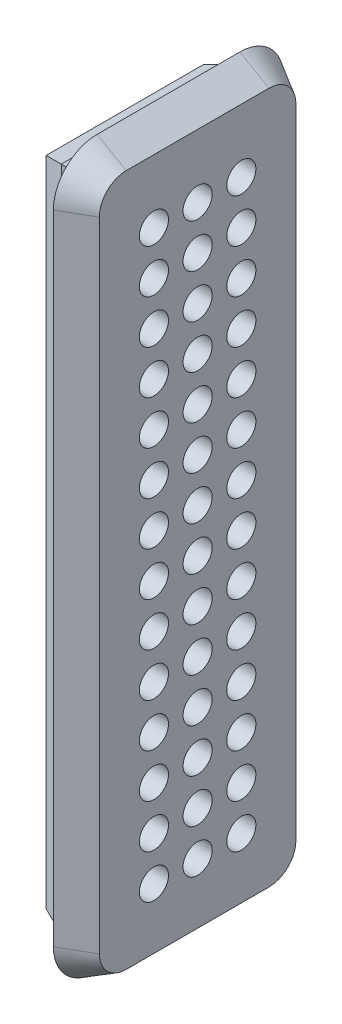
SolidWorks part; units mm, degrees
ref_plane "前视基准面" through (0, 0, 0) normal (0, 0, 1) x (1, 0, 0)
ref_plane "上视基准面" through (0, 0, 0) normal (0, 1, 0) x (1, 0, 0)
ref_plane "右视基准面" through (0, 0, 0) normal (1, 0, 0) x (0, 0, -1)
other "Configuration Table"
sketch "草图1" plane through (0, 0, 0) normal (1, 0, 0) x (0, 0, -1)
  line L0 (-147.2592, 68.0612) -> (-135.4592, 68.0612)
  line L1 (-147.3592, 68.1612) -> (-135.3592, 68.1612) construction
  line L2 (-147.3592, 68.1612) -> (-147.3592, 22.1612) construction
  line L3 (-147.3592, 22.1612) -> (-135.3592, 22.1612) construction
  line L4 (-135.3592, 68.1612) -> (-135.3592, 22.1612) construction
  line L5 (-135.4592, 68.0612) -> (-135.4592, 22.2612)
  line L6 (-147.2592, 22.2612) -> (-135.4592, 22.2612)
  line L7 (-147.2592, 68.0612) -> (-147.2592, 22.2612)
  line L8 (-145.7592, 66.5612) -> (-145.7592, 23.7612)
  line L9 (-145.7592, 23.7612) -> (-136.9592, 23.7612)
  line L10 (-136.9592, 66.5612) -> (-136.9592, 23.7612)
  line L11 (-145.7592, 66.5612) -> (-136.9592, 66.5612)
  dimension "D1" = 12
  dimension "D2" = 46
  dimension "D3" = 0.1
  dimension "D4" = 1.5
extrude "凸台-拉伸1" add sketch "草图1" along normal blind 3
sketch "草图2" plane through (3, 0, 0) normal (1, 0, 0) x (0, 0, -1)
  line L12 (-149.2592, 20.2612) -> (-133.4592, 20.2612)
  line L13 (-149.2592, 70.0612) -> (-149.2592, 20.2612)
  line L14 (-133.4592, 70.0612) -> (-149.2592, 70.0612)
  line L15 (-133.4592, 20.2612) -> (-133.4592, 70.0612)
  line L16 (-146.2592, 20.2612) -> (-136.4592, 20.2612)
  line L17 (-149.2592, 67.0612) -> (-149.2592, 23.2612)
  line L18 (-136.4592, 70.0612) -> (-146.2592, 70.0612)
  line L19 (-133.4592, 23.2612) -> (-133.4592, 67.0612)
  arc A0 (-136.4592, 70.0612) -> (-133.4592, 67.0612) centre (-136.4592, 67.0612) cw
  arc A1 (-136.4592, 20.2612) -> (-133.4592, 23.2612) centre (-136.4592, 23.2612) ccw
  arc A2 (-146.2592, 20.2612) -> (-149.2592, 23.2612) centre (-146.2592, 23.2612) cw
  arc A3 (-149.2592, 67.0612) -> (-146.2592, 70.0612) centre (-146.2592, 67.0612) cw
  dimension "D2" = 3
  dimension "D1" = 2
extrude "凸台-拉伸2" add sketch "草图2" along normal blind 2 draft 30
sketch "草图3" plane through (3, 0, 0) normal (-1, 0, 0) x (0, 0, 1)
  line L0 (136.4592, 70.0612) -> (146.2592, 70.0612) construction
  circle A1 centre (144.3592, 64.5612) radius 1
  circle A2 centre (141.3592, 64.5612) radius 1
  circle A3 centre (138.3592, 64.5612) radius 1
  circle A4 centre (141.3592, 61.5612) radius 1
  circle A5 centre (138.3592, 61.5612) radius 1
  circle A6 centre (141.3592, 58.5612) radius 1
  circle A7 centre (138.3592, 58.5612) radius 1
  circle A8 centre (141.3592, 55.5612) radius 1
  circle A9 centre (138.3592, 55.5612) radius 1
  circle A10 centre (141.3592, 52.5612) radius 1
  circle A11 centre (138.3592, 52.5612) radius 1
  circle A12 centre (141.3592, 49.5612) radius 1
  circle A13 centre (138.3592, 49.5612) radius 1
  circle A14 centre (141.3592, 46.5612) radius 1
  circle A15 centre (138.3592, 46.5612) radius 1
  circle A16 centre (141.3592, 43.5612) radius 1
  circle A17 centre (138.3592, 43.5612) radius 1
  circle A18 centre (141.3592, 40.5612) radius 1
  circle A19 centre (138.3592, 40.5612) radius 1
  circle A20 centre (141.3592, 37.5612) radius 1
  circle A21 centre (138.3592, 37.5612) radius 1
  circle A22 centre (141.3592, 34.5612) radius 1
  circle A23 centre (138.3592, 34.5612) radius 1
  circle A24 centre (141.3592, 31.5612) radius 1
  circle A25 centre (138.3592, 31.5612) radius 1
  circle A26 centre (141.3592, 28.5612) radius 1
  circle A27 centre (138.3592, 28.5612) radius 1
  circle A28 centre (141.3592, 25.5612) radius 1
  circle A29 centre (138.3592, 25.5612) radius 1
  circle A30 centre (144.3592, 61.5612) radius 1
  circle A31 centre (144.3592, 58.5612) radius 1
  circle A32 centre (144.3592, 55.5612) radius 1
  circle A33 centre (144.3592, 52.5612) radius 1
  circle A34 centre (144.3592, 49.5612) radius 1
  circle A35 centre (144.3592, 46.5612) radius 1
  circle A36 centre (144.3592, 43.5612) radius 1
  circle A37 centre (144.3592, 40.5612) radius 1
  circle A38 centre (144.3592, 37.5612) radius 1
  circle A39 centre (144.3592, 34.5612) radius 1
  circle A40 centre (144.3592, 31.5612) radius 1
  circle A41 centre (144.3592, 28.5612) radius 1
  circle A42 centre (144.3592, 25.5612) radius 1
  point P4 (141.3592, 70.0612)
  dimension "D1" = 2
  dimension "D2" = 5.5
  dimension "D4" = 3
  dimension "D5" = 14
extrude "切除-拉伸1" cut sketch "草图3" against normal up to next (2 mm away)
chamfer "倒角1" distance 0.5 angle 72 4 edges at (0, 68.0612, 141.3592) (0, 45.1612, 135.4592) (0, 22.2612, 141.3592) (0, 45.1612, 147.2592) first distance on face at (0, 45.1612, 141.3592)
